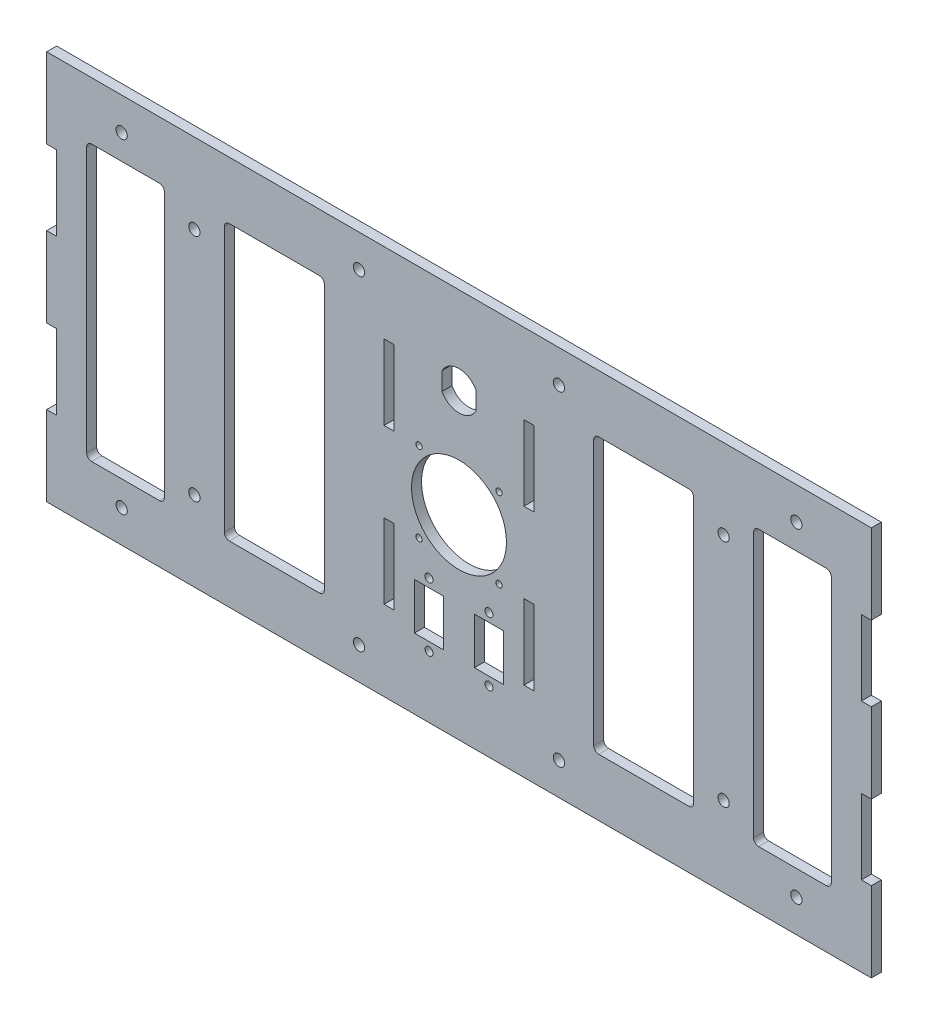
SolidWorks part; units mm, degrees
ref_plane "Ebene vorne" through (0, 0, 0) normal (0, 0, 1) x (1, 0, 0)
ref_plane "Ebene oben" through (0, 0, 0) normal (0, 1, 0) x (1, 0, 0)
ref_plane "Ebene rechts" through (0, 0, 0) normal (1, 0, 0) x (0, 0, -1)
sketch "Skizze1" plane through (0, 0, 0) normal (0, 0, 1) x (1, 0, 0)
  line L1 (165, -78) -> (-165, -78)
  line L2 (165, -78) -> (165, 78)
  line L3 (165, 78) -> (-165, 78)
  line L4 (-165, -78) -> (-165, 78)
  line L5 (165, -78) -> (-165, 78) construction
  line L6 (165, 78) -> (-165, -78) construction
  point P0 (0, 0)
  dimension "D1" = 156
  dimension "D2" = 330
extrude "Aufsatz-Linear austragen1" add sketch "Skizze1" along normal blind 4
sketch "Skizze2" plane through (0, 0, 4) normal (0, 0, 1) x (1, 0, 0)
  line L0 (-165, 65) -> (165, 65) construction
  line L1 (-165, 78) -> (-165, -78) construction
  line L2 (165, -78) -> (165, 78) construction
  line L3 (0, 78) -> (0, -78) construction
  line L4 (165, 78) -> (-165, 78) construction
  line L5 (-165, -78) -> (165, -78) construction
  line L6 (-165, -65) -> (165, -65) construction
  line L7 (-105.9, 65) -> (-105.9, -65) construction
  line L8 (105.9, 65) -> (105.9, -65) construction
  line L9 (-165, 46) -> (165, 46) construction
  line L10 (-165, -46) -> (165, -46) construction
  line L11 (149, -55) -> (117.9, -55)
  line L12 (-149, 55) -> (-117.9, 55)
  line L13 (-149, 55) -> (-149, -55)
  line L14 (-149, -55) -> (-117.9, -55)
  line L15 (-117.9, 55) -> (-117.9, -55)
  line L16 (117.9, 55) -> (117.9, -55)
  line L17 (149, 55) -> (117.9, 55)
  line L18 (149, 55) -> (149, -55)
  line L19 (-40, 65) -> (-40, -65) construction
  line L20 (40, 65) -> (40, -65) construction
  line L21 (-165, 0) -> (165, 0) construction
  line L28 (-25.9951, 0) -> (-40, -11.9903) construction
  line L34 (-135, 65) -> (-135, -65) construction
  circle A2 centre (-105.9, 46) radius 2.25
  circle A3 centre (-105.9, -46) radius 2.25
  circle A4 centre (105.9, -46) radius 2.25
  circle A5 centre (105.9, 46) radius 2.25
  circle A6 centre (-40, 65) radius 2.25
  circle A7 centre (40, 65) radius 2.25
  circle A8 centre (-40, -65) radius 2.25
  circle A9 centre (40, -65) radius 2.25
  circle A10 centre (-135, -65) radius 2.25
  circle A11 centre (-135, 65) radius 2.25
  circle A12 centre (135, -65) radius 2.25
  circle A13 centre (135, 65) radius 2.25
  point P48 (-25.9951, 0)
  point P57 (25.9951, 0)
  dimension "D3" = 4.5
  dimension "D1" = 13
  dimension "D2" = 13
  dimension "D4" = 59.1
  dimension "D5" = 59.1
  dimension "D6" = 32
  dimension "D7" = 32
  dimension "D8" = 23
  dimension "D9" = 23
  dimension "D12" = 40
  dimension "D13" = 40
  dimension "D11" = 16
extrude "Schnitt-Linear austragen1" cut sketch "Skizze2" against normal through all
sketch "Skizze3" plane through (0, 0, 4) normal (0, 0, 1) x (1, 0, 0)
  line L0 (0, 78) -> (0, -78) construction
  line L1 (165, 78) -> (-165, 78) construction
  line L2 (-165, -78) -> (165, -78) construction
  line L4 (-20, -20) -> (20, -20) construction
  line L5 (-20, -20) -> (-20, 20) construction
  line L6 (-20, 20) -> (20, 20) construction
  line L7 (20, -20) -> (20, 20) construction
  line L8 (-20, -20) -> (20, 20) construction
  line L9 (-20, 20) -> (20, -20) construction
  line L10 (-16, -16) -> (16, -16) construction
  line L11 (-16, -16) -> (-16, 16) construction
  line L12 (-16, 16) -> (16, 16) construction
  line L13 (16, -16) -> (16, 16) construction
  line L14 (-16, -16) -> (16, 16) construction
  line L15 (-16, 16) -> (16, -16) construction
  point P6 (0, 0)
  point P11 (0, 0)
  point P12 (16, 16)
  point P14 (-16, -16)
  point P15 (-16, 16)
  point P16 (16, -16)
  dimension "D1" = 40
  dimension "D3" = 32
hole_wizard "M3 Gewindebohrung1" positions "Skizze3" profile "Skizze4" tap size "M3" standard "DIN" end condition through all
sketch "Skizze4" plane through (16, -16, 4) normal (1, 0, 0) x (0, -1, 0)
  line L0 (0, 0) -> (0, 4)
  line L1 (0, 4) -> (1.25, 4)
  line L2 (1.25, 4) -> (1.25, 0)
  line L5 (1.25, 0) -> (0, 0)
  line L11 (0, -6.35) -> (0, 107.95) construction
  dimension "Bohrerdurchmesser" = 2.5
  dimension "Bohrungstiefe" = 4
sketch "Skizze5" plane through (0, 0, 4) normal (0, 0, 1) x (1, 0, 0)
  circle A0 centre (0, 0) radius 19
  dimension "D1" = 38
extrude "Schnitt-Linear austragen2" cut sketch "Skizze5" against normal through all contours A0
fillet "Verrundung1" radius 2 8 edges at (149, 55, 2) (117.9, 55, 2) (149, -55, 2) (117.9, -55, 2) (-149, -55, 2) (-117.9, -55, 2) (-117.9, 55, 2) (-149, 55, 2)
sketch "Skizze7" plane through (0, 0, 4) normal (0, 0, 1) x (1, 0, 0)
  line L0 (-30.2968, -0.8563) -> (29.426, -0.8563) construction
  line L1 (-12, -53.2802) -> (-12, -27.8802) construction
  line L6 (-6.8, 46.6125) -> (-6.8, 39.3875)
  line L7 (6.8, 46.6125) -> (6.8, 39.3875)
  line L8 (0, 73.9526) -> (0, -71.9477) construction
  line L9 (-6.15, -49.8802) -> (-17.85, -49.8802)
  line L10 (-6.15, -49.8802) -> (-6.15, -31.2802)
  line L11 (-6.15, -31.2802) -> (-17.85, -31.2802)
  line L12 (-17.85, -49.8802) -> (-17.85, -31.2802)
  line L13 (-6.15, -49.8802) -> (-17.85, -31.2802) construction
  line L14 (-6.15, -31.2802) -> (-17.85, -49.8802) construction
  line L15 (6.15, -31.2802) -> (17.85, -49.8802) construction
  line L16 (6.15, -49.8802) -> (17.85, -31.2802) construction
  line L17 (12, -53.2802) -> (12, -27.8802) construction
  line L18 (17.85, -49.8802) -> (17.85, -31.2802)
  line L19 (6.15, -31.2802) -> (17.85, -31.2802)
  line L20 (6.15, -49.8802) -> (6.15, -31.2802)
  line L21 (6.15, -49.8802) -> (17.85, -49.8802)
  line L22 (165, 78) -> (-165, 78) construction
  circle A2 centre (-12, -27.8802) radius 1.6
  circle A3 centre (-12, -53.2802) radius 1.6
  circle A4 centre (12, -53.2802) radius 1.6
  circle A5 centre (12, -27.8802) radius 1.6
  arc A6 (-6.8, 39.3875) -> (6.8, 39.3875) centre (0, 43) ccw
  arc A7 (6.8, 46.6125) -> (-6.8, 46.6125) centre (0, 43) ccw
  point P15 (-12, -40.5802)
  point P30 (12, -40.5802)
  dimension "D8" = 3.2
  dimension "D2" = 15.4
  dimension "D9" = 18.6
  dimension "D10" = 11.7
  dimension "D11" = 25.4
  dimension "D12" = 12
  dimension "D3" = 13.6
  dimension "D4" = 6.8
  dimension "D5" = 35
extrude "Schnitt-Linear austragen3" cut sketch "Skizze7" against normal through all
sketch "Skizze9" plane through (0, 0, 4) normal (0, 0, 1) x (1, 0, 0)
  line L0 (-117.9, -53) -> (-117.9, 53) construction
  line L1 (-93.9, 55) -> (-53.9, 55)
  line L2 (-93.9, 55) -> (-93.9, 7)
  line L3 (-93.9, -55) -> (-53.9, -55)
  line L4 (-53.9, 55) -> (-53.9, 7)
  line L5 (-119.9, 55) -> (-147, 55) construction
  line L6 (-147, -55) -> (-119.9, -55) construction
  line L7 (-53.9, 0) -> (-93.9, 0) construction
  line L10 (-53.9, -7) -> (-53.9, -55)
  line L11 (-93.9, -7) -> (-93.9, -55)
  line L12 (0, 78) -> (0, -78)
  line L13 (165, 78) -> (-165, 78) construction
  line L14 (-165, -78) -> (165, -78) construction
  line L15 (-93.9, 7) -> (-93.9, 55)
  line L16 (-53.9, 7) -> (-53.9, 55)
  line L17 (53.9, 7) -> (53.9, -7)
  line L18 (93.9, 7) -> (93.9, -7)
  line L19 (-53.9, -55) -> (-53.9, -7)
  line L20 (-93.9, 55) -> (-53.9, 55)
  line L21 (-93.9, -55) -> (-93.9, -7)
  line L22 (-93.9, -55) -> (-53.9, -55)
  line L23 (53.9, 0) -> (93.9, 0) construction
  line L24 (93.9, -55) -> (53.9, -55)
  line L25 (93.9, -55) -> (93.9, -7)
  line L26 (93.9, 55) -> (53.9, 55)
  line L27 (53.9, -55) -> (53.9, -7)
  line L28 (-93.9, 7) -> (-93.9, -7)
  line L29 (-53.9, 7) -> (-53.9, -7)
  line L30 (53.9, 7) -> (53.9, 55)
  line L31 (93.9, 7) -> (93.9, 55)
  line L32 (93.9, -7) -> (93.9, -55)
  line L33 (53.9, -7) -> (53.9, -55)
  line L36 (53.9, 55) -> (53.9, 7)
  line L37 (93.9, -55) -> (53.9, -55)
  line L38 (93.9, 55) -> (93.9, 7)
  line L39 (93.9, 55) -> (53.9, 55)
  line L40 (-93.9, 7) -> (-93.9, -7)
  line L41 (-53.9, 7) -> (-53.9, -7)
  dimension "D1" = 24
  dimension "D2" = 40
extrude "Schnitt-Linear austragen4" cut sketch "Skizze9" against normal through all
fillet "Verrundung2" radius 2 8 edges at (-93.9, -55, 2) (-53.9, -55, 2) (-53.9, 55, 2) (-93.9, 55, 2) (53.9, -55, 2) (93.9, -55, 2) (93.9, 55, 2) (53.9, 55, 2)
sketch "Skizze10" plane through (0, 0, 4) normal (0, 0, 1) x (1, 0, 0)
  line L0 (-165, 78) -> (-165, -78) construction
  line L1 (-26, 16) -> (-30, 16)
  line L2 (-26, 16) -> (-26, 46)
  line L3 (-26, 46) -> (-30, 46)
  line L4 (-30, 16) -> (-30, 46)
  line L5 (-26, 16) -> (-30, 46) construction
  line L6 (-26, 46) -> (-30, 16) construction
  line L9 (165, 78) -> (-165, 78) construction
  line L10 (2.2, 0) -> (-2.2, 0) construction
  line L11 (-26, -46) -> (-30, -16) construction
  line L12 (-26, -16) -> (-30, -46) construction
  line L13 (-30, -16) -> (-30, -46)
  line L14 (-26, -46) -> (-30, -46)
  line L15 (-26, -16) -> (-26, -46)
  line L16 (-26, -16) -> (-30, -16)
  line L17 (0, -2.2) -> (0, 2.2) construction
  line L18 (26, -16) -> (30, -46) construction
  line L19 (26, -46) -> (30, -16) construction
  line L20 (26, 46) -> (30, 16) construction
  line L21 (26, 16) -> (30, 46) construction
  line L22 (26, -16) -> (30, -16)
  line L23 (26, -16) -> (26, -46)
  line L24 (26, -46) -> (30, -46)
  line L25 (30, -16) -> (30, -46)
  line L26 (30, 16) -> (30, 46)
  line L27 (26, 46) -> (30, 46)
  line L28 (26, 16) -> (26, 46)
  line L29 (26, 16) -> (30, 16)
  line L30 (-161, -46) -> (-161, -16)
  line L31 (-165, 46) -> (-161, 46)
  line L32 (-165, 46) -> (-165, 16)
  line L33 (-165, 16) -> (-161, 16)
  line L34 (-161, 46) -> (-161, 16)
  line L35 (-165, -16) -> (-161, -16)
  line L36 (-165, -46) -> (-165, -16)
  line L37 (-165, -46) -> (-161, -46)
  line L38 (165, -46) -> (161, -46)
  line L39 (165, -46) -> (165, -16)
  line L40 (165, -16) -> (161, -16)
  line L41 (161, 46) -> (161, 16)
  line L42 (165, 16) -> (161, 16)
  line L43 (165, 46) -> (165, 16)
  line L44 (165, 46) -> (161, 46)
  line L45 (161, -46) -> (161, -16)
  point P0 (-28, 31)
  point P16 (-28, -31)
  point P27 (28, -31)
  point P28 (28, 31)
  dimension "D1" = 30
  dimension "D2" = 4
  dimension "D3" = 135
  dimension "D4" = 47
  dimension "D5" = 30
  dimension "D6" = 4
  dimension "D7" = 32
extrude "Schnitt-Linear austragen5" cut sketch "Skizze10" against normal through all
equation "\"D13@Skizze2\"=\"D12@Skizze2\""
equation "\"D4@Skizze7\"=\"D3@Skizze7\"/2"
equation "\"D5@Skizze2\"=\"D4@Skizze2\""
equation "\"D2@Skizze2\"=\"D1@Skizze2\""
equation "\"D8@Skizze2\"=\"D9@Skizze2\""
